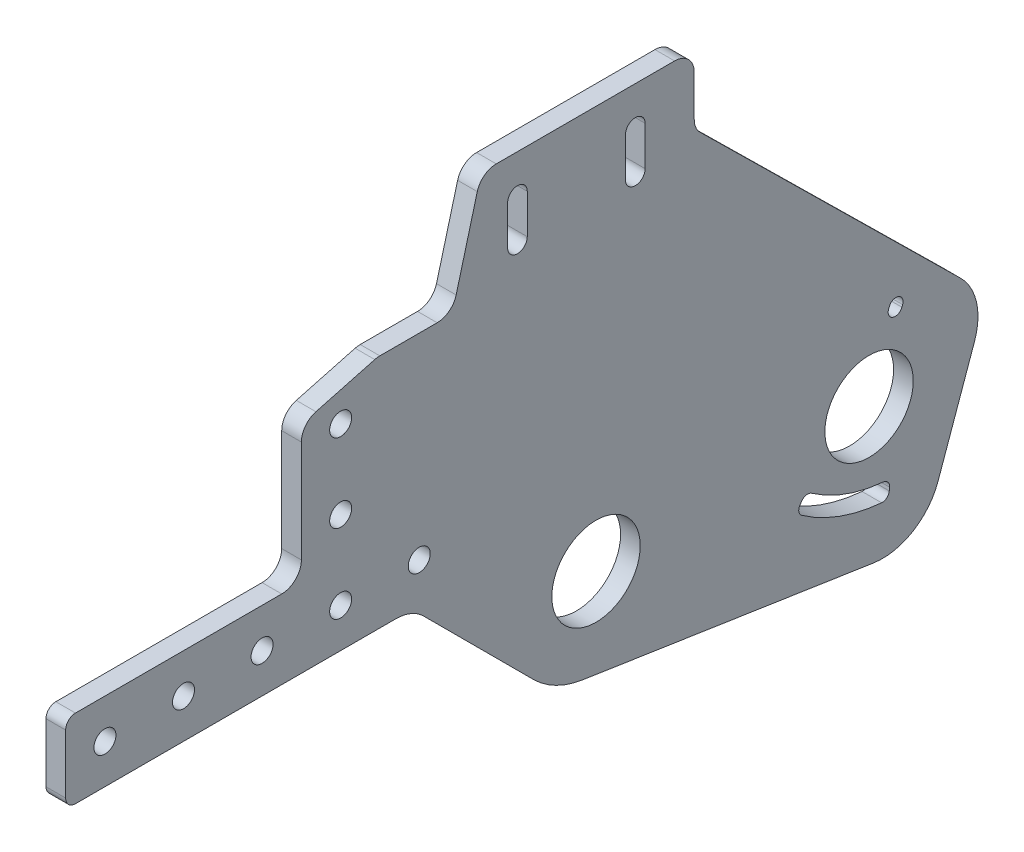
SolidWorks part; units mm, degrees
ref_plane "Front Plane" through (0, 0, 0) normal (0, 0, 1) x (1, 0, 0)
ref_plane "Top Plane" through (0, 0, 0) normal (0, 1, 0) x (1, 0, 0)
ref_plane "Right Plane" through (0, 0, 0) normal (1, 0, 0) x (0, 0, -1)
sketch "Sketch2" plane through (0, 0, 0) normal (1, 0, 0) x (0, 0, -1)
  line L0 (-168.275, 19.05) -> (-64.7217, 19.05)
  line L1 (-4.292, -28.2508) -> (89.7471, -42.5375)
  line L2 (-171.45, 22.225) -> (-171.45, 41.275)
  line L3 (-168.275, 44.45) -> (-101.6, 44.45)
  line L4 (-38.3848, 125.4685) -> (-45.2207, 99.9565)
  line L5 (41.6129, 175.1877) -> (218.62, -77.6046) construction
  line L6 (15.0515, 157.8062) -> (118.3631, 25.535) construction
  line L7 (53.6439, -14.125) -> (-17.3081, 137.9762) construction
  line L8 (-4.6354, 18.5275) -> (78.6163, 39.3564) construction
  line L9 (80.5683, -35.188) -> (-3.6594, -18.7447) construction
  line L10 (96.725, 25.2801) -> (96.9473, 25.8909) construction
  line L11 (55, 0) -> (-55, 0) construction
  line L12 (-20.2056, -20.2056) -> (-55.7414, 15.3303)
  line L13 (0, 95.25) -> (255.6229, 95.25) construction
  line L14 (0, 50.8) -> (255.6229, 50.8) construction
  line L15 (122.3804, 3.2387) -> (110.5619, -30.0732)
  line L16 (31.75, 123.825) -> (31.75, 110.6081)
  line L17 (94.5769, 26.062) -> (94.7992, 26.6728)
  line L18 (98.8732, 24.4983) -> (99.0955, 25.1091)
  line L19 (68.3924, -14.8897) -> (67.8097, -15.722) construction
  line L21 (66.5198, -13.5785) -> (65.9371, -14.4108)
  line L22 (92.6084, -23.7036) -> (92.5198, -24.7158) construction
  line L23 (94.8857, -23.9029) -> (94.7971, -24.915)
  line L26 (96.9473, 25.8909) -> (68.3924, -14.8897) construction
  line L27 (96.9473, 25.8909) -> (92.6084, -23.7036) construction
  line L28 (88.26, 2.0227) -> (96.9473, 25.8909) construction
  line L29 (-95.25, 50.8) -> (-95.25, 83.8035)
  line L30 (-69.8795, 95.25) -> (-51.3544, 95.25)
  line L31 (-71.523, 95.0336) -> (-90.5435, 89.9371)
  line L32 (0, 0) -> (87.8872, 2.3014) construction
  line L33 (0, 146.05) -> (88.26, 2.0227) construction
  line L34 (0, 55) -> (0, -55) construction
  line L35 (33.6435, 106.0845) -> (117.7963, 23.1789)
  line L36 (-32.2512, 130.175) -> (25.4, 130.175)
  line L37 (-25.4, 117.475) -> (-25.4, 104.775) construction
  line L38 (-22.225, 117.475) -> (-22.225, 104.775)
  line L39 (-28.575, 117.475) -> (-28.575, 104.775)
  line L40 (12.7, 117.475) -> (12.7, 104.775) construction
  line L41 (15.875, 117.475) -> (15.875, 104.775)
  line L42 (9.525, 117.475) -> (9.525, 104.775)
  circle A0 centre (0, 146.05) radius 14.2875 construction
  circle A1 centre (0, 0) radius 14.2875
  circle A2 centre (0, 146.05) radius 50.8 construction
  circle A3 centre (0, 0) radius 50.8 construction
  circle A5 centre (-57.15, 31.75) radius 3.556
  circle A6 centre (-82.55, 31.75) radius 3.556
  circle A7 centre (-107.95, 31.75) radius 3.556
  circle A8 centre (-133.35, 31.75) radius 3.556
  circle A9 centre (-158.75, 31.75) radius 3.556
  arc A10 (31.75, 146.05) -> (-30.6681, 154.2675) centre (0, 146.05) ccw construction
  arc A11 (-171.45, 41.275) -> (-168.275, 44.45) centre (-168.275, 41.275) cw
  arc A12 (-168.275, 19.05) -> (-171.45, 22.225) centre (-168.275, 22.225) cw
  arc A14 (-55.7414, 15.3303) -> (-64.7217, 19.05) centre (-64.7217, 6.35) ccw
  arc A15 (-4.6354, 18.5275) -> (-3.6594, -18.7447) centre (0, 0) ccw construction
  arc A16 (15.0515, 157.8062) -> (-17.3081, 137.9762) centre (0, 146.05) ccw construction
  arc A17 (53.6439, -14.125) -> (118.3631, 25.535) centre (88.26, 2.0227) ccw construction
  arc A18 (80.5683, -35.188) -> (78.6163, 39.3564) centre (87.8872, 2.3014) ccw construction
  circle A19 centre (87.8872, 2.3014) radius 32 construction
  circle A20 centre (88.26, 2.0227) radius 32 construction
  circle A21 centre (88.26, 2.0227) radius 24.75 construction
  circle A24 centre (87.8872, 2.3014) radius 24.75 construction
  arc A29 (-20.2056, -20.2056) -> (-4.292, -28.2508) centre (0, 0) ccw
  arc A30 (122.3804, 3.2387) -> (117.7963, 23.1789) centre (104.4268, 9.6083) ccw
  arc A31 (89.7471, -42.5375) -> (110.5619, -30.0732) centre (92.6084, -23.7036) ccw
  circle A32 centre (88.26, 2.0227) radius 14.2875
  circle A33 centre (87.8872, 2.3014) radius 14.2875 construction
  arc A34 (94.5769, 26.062) -> (98.8732, 24.4983) centre (96.725, 25.2801) ccw
  arc A35 (99.0955, 25.1091) -> (94.7992, 26.6728) centre (96.9473, 25.8909) ccw
  arc A37 (65.9371, -14.4108) -> (66.4985, -17.5946) centre (67.8097, -15.722) ccw
  arc A38 (94.8857, -23.9029) -> (92.8076, -21.4263) centre (92.6084, -23.7036) ccw
  arc A39 (92.3206, -26.9931) -> (94.7971, -24.915) centre (92.5198, -24.7158) ccw
  arc A40 (69.7036, -13.0172) -> (92.8076, -21.4263) centre (96.9473, 25.8909) ccw
  arc A41 (66.4985, -17.5946) -> (92.3206, -26.9931) centre (96.9473, 25.8909) ccw
  arc A42 (69.7036, -13.0172) -> (66.5198, -13.5785) centre (68.3924, -14.8897) ccw
  circle A43 centre (-82.55, 57.15) radius 3.556
  circle A44 centre (-82.55, 82.55) radius 3.556
  arc A45 (-51.3544, 95.25) -> (-45.2207, 99.9565) centre (-51.3544, 101.6) ccw
  arc A46 (-95.25, 50.8) -> (-101.6, 44.45) centre (-101.6, 50.8) cw
  arc A48 (-90.5435, 89.9371) -> (-95.25, 83.8035) centre (-88.9, 83.8035) ccw
  arc A49 (-71.523, 95.0336) -> (-69.8795, 95.25) centre (-69.8795, 88.9) cw
  arc A50 (33.6435, 106.0845) -> (31.75, 110.6081) centre (38.1, 110.6081) cw
  arc A53 (25.4, 130.175) -> (31.75, 123.825) centre (25.4, 123.825) cw
  arc A54 (-32.2512, 130.175) -> (-38.3848, 125.4685) centre (-32.2512, 123.825) ccw
  arc A55 (-22.225, 117.475) -> (-28.575, 117.475) centre (-25.4, 117.475) ccw
  arc A56 (-28.575, 104.775) -> (-22.225, 104.775) centre (-25.4, 104.775) ccw
  arc A57 (15.875, 117.475) -> (9.525, 117.475) centre (12.7, 117.475) ccw
  arc A58 (9.525, 104.775) -> (15.875, 104.775) centre (12.7, 104.775) ccw
  point P50 (96.8362, 25.5855)
  point P57 (0, 0)
  point P74 (4.5986, 110.6081)
  point P76 (-95.25, 88.676)
  point P79 (102.7469, -16.3909)
  point P97 (-70.7155, 95.25)
  point P104 (-25.4, 111.125)
  point P113 (31.75, 107.95)
  point P115 (0, 0)
  point P116 (0, 0)
  point P122 (0, 0)
  point P123 (0, 0)
  point P124 (12.7, 111.125)
  dimension "D1" = 28.575
  dimension "D2" = 101.6
  dimension "D3" = 44.45
  dimension "D4" = 19.05
  dimension "D6" = 57.15
  dimension "D8" = 7.112
  dimension "D14" = 105
  dimension "D15" = 3.175
  dimension "D16" = 12.7
  dimension "D18" = 38.1972
  dimension "D19" = 76.3944
  dimension "D20" = 520
  dimension "D21" = 360
  dimension "D22" = 64
  dimension "D23" = 49.5
  dimension "D24" = 4.572
  dimension "D25" = 19.05
  dimension "D26" = 31.75
  dimension "D27" = 25.4
  dimension "D28" = 2.286
  dimension "D29" = 1.016
  dimension "D36" = 25.4
  dimension "D38" = 12.7
  dimension "D39" = 6.35
  dimension "D40" = 15
  dimension "D42" = 6.35
  dimension "D43" = 5.588
  dimension "D44" = 58.5
  dimension "D47" = 31.75
  dimension "D48" = 12.7
  dimension "D50" = 6.35
  dimension "D51" = 12.7
  dimension "D52" = 15.875
  dimension "D53" = 12.7
  dimension "D55" = 25.4
  dimension "D56" = 6.35
  dimension "D5" = 135
  dimension "D7" = 12.7
  dimension "D9" = 57.15
  dimension "D10" = 12.7
  dimension "D12" = 25.4
  dimension "D13" = 12.7
  dimension "D17" = 55
  dimension "D30" = 3
  dimension "D31" = 30
  dimension "D32" = 15
  dimension "D33" = 50.8
  dimension "D34" = 50.8
  dimension "D35" = 1.016
  dimension "D37" = 12.7
  dimension "D41" = 25.4
  dimension "D45" = 1.5
  dimension "D46" = 110
  dimension "D49" = 12.7
  dimension "D57" = 6.35
  dimension "D58" = 12.7
  dimension "D11" = 5
extrude "Boss-Extrude1" add sketch "Sketch2" along normal blind 6.35
